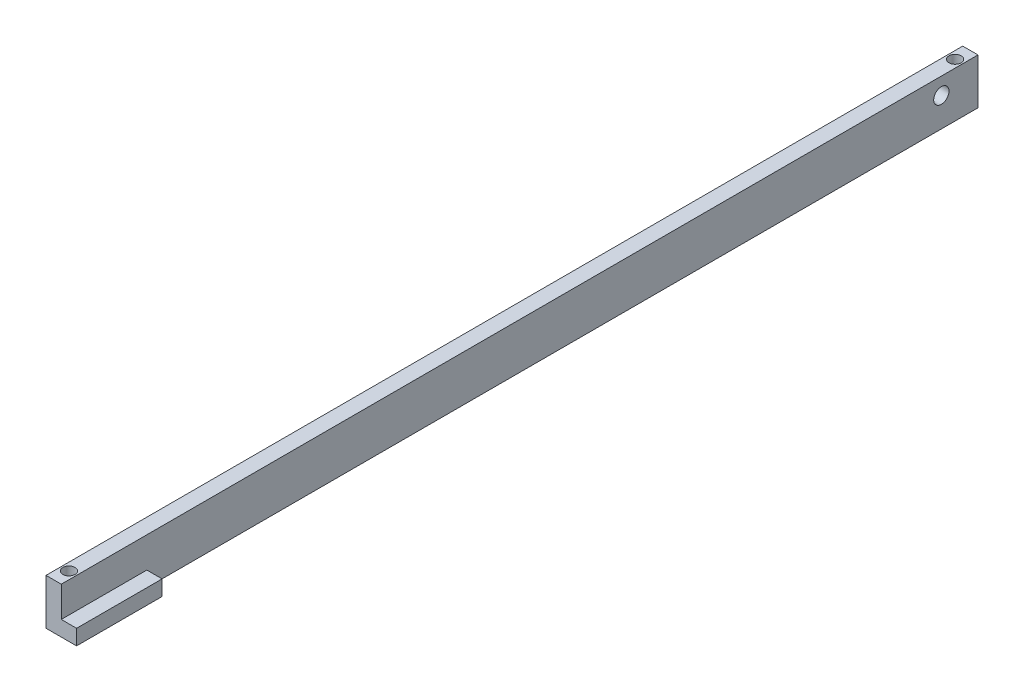
SolidWorks part; units mm, degrees
other "Markup1"
sketch "Sketch6" plane through (0, 0, 0) normal (0.7258, -0.6292, 0.2781) x (-0.261, -0.6259, -0.735)
ref_plane "Front Plane" through (0, 0, 0) normal (0, 0, 1) x (1, 0, 0)
ref_plane "Top Plane" through (0, 0, 0) normal (0, 1, 0) x (1, 0, 0)
ref_plane "Right Plane" through (0, 0, 0) normal (1, 0, 0) x (0, 0, -1)
sketch "Sketch1" plane through (0, 0, 0) normal (0, 0, 1) x (1, 0, 0)
  line L0 (0, 0) -> (-12.7, 0)
  line L1 (-12.7, 0) -> (-12.7, 19.05)
  line L2 (-12.7, 19.05) -> (-6.35, 19.05)
  line L3 (-6.35, 19.05) -> (-6.35, 6.35)
  line L4 (-6.35, 6.35) -> (0, 6.35)
  line L5 (0, 6.35) -> (0, 0)
  dimension "D1" = 6.35
  dimension "D2" = 6.35
  dimension "D3" = 6.35
  dimension "D4" = 12.7
extrude "Boss-Extrude1" add sketch "Sketch1" against normal blind 381
sketch "Sketch2" plane through (-12.7, 0, 0) normal (-1, 0, 0) x (0, 0, 1)
  line L0 (-381, 0) -> (0, 0) construction
  line L2 (0, 19.05) -> (0, 0) construction
  circle A0 centre (-365.76, 12.065) radius 3.175
  dimension "D1" = 6.35
  dimension "D2" = 12.065
  dimension "D3" = 365.76
extrude "Cut-Extrude1" cut sketch "Sketch2" against normal up to next
sketch "Sketch3" plane through (0, 19.05, 0) normal (0, 1, 0) x (1, 0, 0)
  line L0 (-9.525, 381) -> (-9.525, 0) construction
  line L1 (-6.35, 381) -> (-12.7, 381) construction
  line L2 (-6.35, 0) -> (-12.7, 0) construction
  circle A0 centre (-9.525, 6.35) radius 2.54
  circle A1 centre (-9.525, 374.65) radius 2.54
  dimension "D1" = 5.08
  dimension "D3" = 6.35
  dimension "D2" = 6.35
extrude "Cut-Extrude2" cut sketch "Sketch3" against normal blind 7.62
sketch "Sketch4" plane through (0, 0, 0) normal (0, -1, 0) x (1, 0, 0)
  line L0 (-9.525, 0) -> (-9.525, -381) construction
  line L1 (-12.7, 0) -> (0, 0) construction
  line L2 (-12.7, -381) -> (0, -381) construction
  line L3 (0, -381) -> (0, 0) construction
  circle A0 centre (-9.525, -374.65) radius 2.54
  circle A1 centre (-9.525, -6.35) radius 2.54
  dimension "D2" = 5.08
  dimension "D1" = 9.525
  dimension "D3" = 6.35
  dimension "D4" = 6.35
extrude "Cut-Extrude3" cut sketch "Sketch4" against normal blind 7.62
sketch "Sketch5" plane through (0, 0, -381) normal (0, 0, -1) x (-1, 0, 0)
  line L1 (6.35, 6.35) -> (0, 6.35)
  line L2 (6.35, 6.35) -> (6.35, 0)
  line L3 (6.35, 0) -> (0, 0)
  line L4 (0, 6.35) -> (0, 0)
extrude "Cut-Extrude4" cut sketch "Sketch5" against normal blind 345.44
